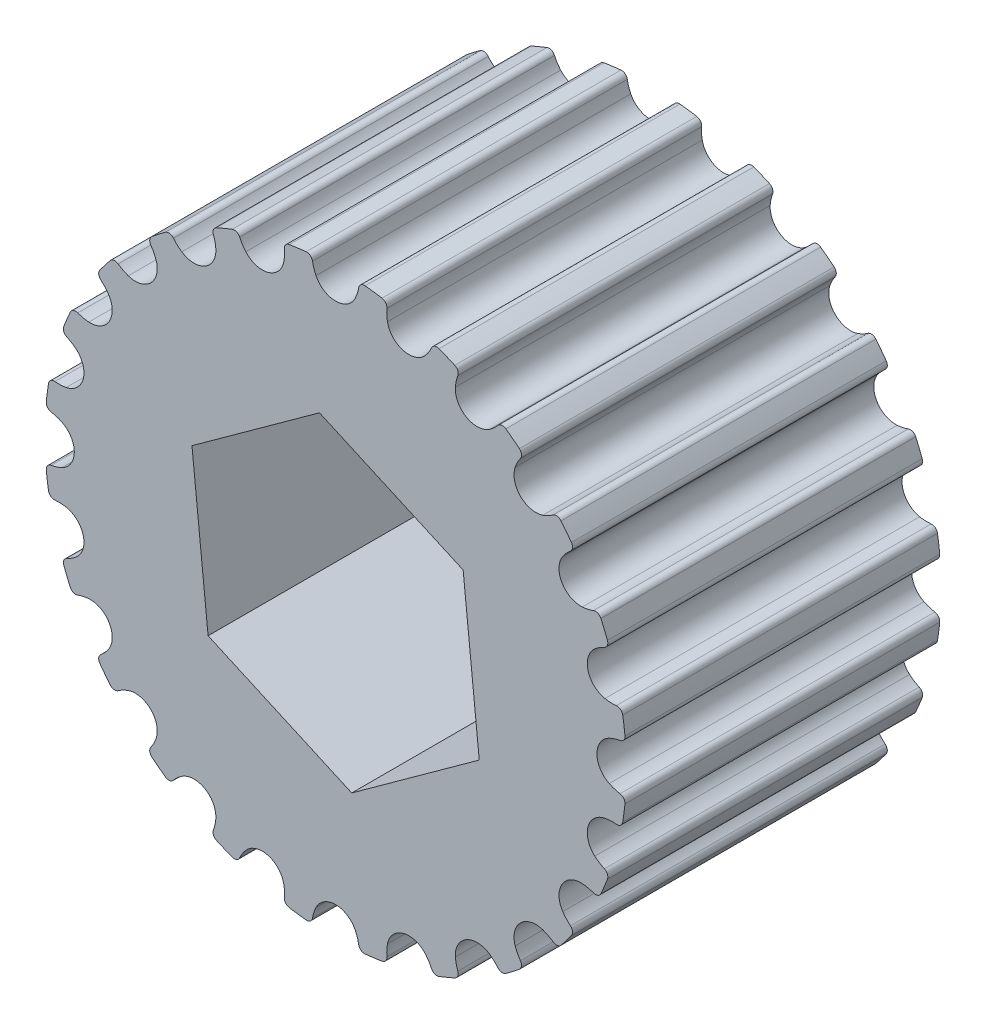
SolidWorks part; units mm, degrees
ref_plane "Front Plane" through (0, 0, 0) normal (0, 0, 1) x (1, 0, 0)
ref_plane "Top Plane" through (0, 0, 0) normal (0, 1, 0) x (1, 0, 0)
ref_plane "Right Plane" through (0, 0, 0) normal (1, 0, 0) x (0, 0, -1)
sketch "Sketch1" plane through (0, 0, 0) normal (0, 0, 1) x (1, 0, 0)
  line L1 (-1.7022, 6.6415) -> (1.7835, 6.6415) construction
  line L4 (0, 0) -> (0, 6.6415) construction
  line L6 (0, 7.6455) -> (1.9828, 7.3839) construction
  line L7 (1.9828, 7.3839) -> (2.7252, 7.1845) construction
  line L8 (1.9828, 7.3839) -> (1.7835, 6.6415) construction
  line L9 (-1.7434, 6.6996) -> (-1.7022, 6.6415) construction
  line L10 (-2.032, 7.1067) -> (-2.4139, 7.6455)
  line L11 (-2.4139, 7.6455) -> (2.0531, 7.6455)
  line L12 (2.0531, 7.6455) -> (1.9169, 7.1386)
  circle A0 centre (0, 0) radius 7.6455 construction
  circle A2 centre (0, 0) radius 7.3915 construction
  arc A3 (-0.4989, 6.9533) -> (0.4989, 6.9533) centre (0, 7.1965) ccw
  arc A4 (-0.4989, 6.9533) -> (-0.5866, 7.2286) centre (0.4, 7.3915) cw
  arc A5 (-2.032, 7.1067) -> (-0.7499, 7.3534) centre (0, 0) cw
  arc A6 (-0.5866, 7.2286) -> (-0.7499, 7.3534) centre (-0.7346, 7.2041) ccw
  arc A7 (1.9169, 7.1386) -> (0.7499, 7.3534) centre (0, 0) ccw
  arc A8 (0.5866, 7.2286) -> (0.7499, 7.3534) centre (0.7346, 7.2041) cw
  arc A9 (0.4989, 6.9533) -> (0.5866, 7.2286) centre (-0.4, 7.3915) ccw
  point P3 (0, 0)
  point P5 (0, 0)
  point P6 (0, 0)
  point P7 (0, 0)
  point P8 (0, 0)
  point P10 (0, 0)
  point P11 (0, 7.6455)
  point P13 (0, 0)
  point P14 (0, 7.3915)
  point P30 (0, 0)
  point P38 (0, 0)
  point P39 (0, 0)
  point P40 (0, 0)
  point P41 (0, 0)
  point P42 (0, 0)
  point P43 (0, 0)
  dimension "PD" = 15.291
  dimension "R3" = 0.555
  dimension "R2" = 1
  dimension "R1" = 0.15
  dimension "b" = 0.4
  dimension "D3" = 2
  dimension "PLD" = 0.254
  dimension "h" = 0.75
sketch "Sketch2" plane through (0, 0, 0) normal (1, 0, 0) x (0, 0, -1)
  line L1 (-4, 0) -> (-4, 7.3915)
  line L6 (-4, 7.3915) -> (4, 7.3915)
  line L9 (4, 7.3915) -> (4, 0)
  line L10 (-4, 0) -> (4, 0)
  dimension "Inside Width" = 8
revolve "Revolve1" add sketch "Sketch2" angle 360 mid plane about L10
sketch "Sketch3" plane through (0, 0, 0) normal (0, 0, 1) x (1, 0, 0)
  line L6 (2.0531, 7.6455) -> (-2.4139, 7.6455)
  line L7 (1.9169, 7.1386) -> (2.0531, 7.6455)
  line L8 (-2.4139, 7.6455) -> (-2.032, 7.1067)
  line L9 (2.0531, 7.6455) -> (-2.4139, 7.6455)
  line L10 (1.9169, 7.1386) -> (2.0531, 7.6455)
  line L11 (-2.4139, 7.6455) -> (-2.032, 7.1067)
  arc A8 (1.9169, 7.1386) -> (0.7499, 7.3534) centre (0, 0) ccw
  arc A9 (0.7499, 7.3534) -> (0.5866, 7.2286) centre (0.7346, 7.2041) ccw
  arc A10 (0.4989, 6.9533) -> (0.5866, 7.2286) centre (-0.4, 7.3915) ccw
  arc A11 (-0.4989, 6.9533) -> (0.4989, 6.9533) centre (0, 7.1965) ccw
  arc A12 (-0.5866, 7.2286) -> (-0.4989, 6.9533) centre (0.4, 7.3915) ccw
  arc A13 (-0.5866, 7.2286) -> (-0.7499, 7.3534) centre (-0.7346, 7.2041) ccw
  arc A14 (-0.7499, 7.3534) -> (-2.032, 7.1067) centre (0, 0) ccw
  arc A15 (1.9169, 7.1386) -> (0.7499, 7.3534) centre (0, 0) ccw
  arc A16 (0.7499, 7.3534) -> (0.5866, 7.2286) centre (0.7346, 7.2041) ccw
  arc A17 (0.4989, 6.9533) -> (0.5866, 7.2286) centre (-0.4, 7.3915) ccw
  arc A18 (-0.4989, 6.9533) -> (0.4989, 6.9533) centre (0, 7.1965) ccw
  arc A19 (-0.5866, 7.2286) -> (-0.4989, 6.9533) centre (0.4, 7.3915) ccw
  arc A20 (-0.5866, 7.2286) -> (-0.7499, 7.3534) centre (-0.7346, 7.2041) ccw
  arc A21 (-0.7499, 7.3534) -> (-2.032, 7.1067) centre (0, 0) ccw
  dimension "D1" = 0
extrude "Cut-Extrude1" cut sketch "Sketch3" against normal up to next from surface starting at face at (7.3915, 0, 4)
pattern_circular "CirPattern1" count 24 over 360 about axis through (0, 0, 4) along (0, 0, 1) of "Cut-Extrude1"
sketch "Sketch4" plane through (0, 0, 4) normal (0, 0, 1) x (1, 0, 0)
  line L1 (0.4098, -3.979) -> (3.6508, -1.6346)
  line L2 (3.6508, -1.6346) -> (3.241, 2.3444)
  line L3 (3.241, 2.3444) -> (-0.4098, 3.979)
  line L4 (-0.4098, 3.979) -> (-3.6508, 1.6346)
  line L5 (-3.6508, 1.6346) -> (-3.241, -2.3444)
  line L6 (-3.241, -2.3444) -> (0.4098, -3.979)
  circle A0 centre (0, 0) radius 3.4641 construction
  circle A1 centre (0, 0) radius 4 construction
  dimension "D1" = 8
extrude "Cut-Extrude2" cut sketch "Sketch4" against normal up to next
ref_axis "Center Axis 1" through (0, 0, -7.135) along (0, 0, 1)
ref_plane "Contact Plane 1" through (0, 0, 7.135) normal (0, 0, 1) x (1, 0, 0)
ref_plane "Contact Plane 2" through (0, 0, -7.135) normal (0, 0, -1) x (-1, 0, 0)
